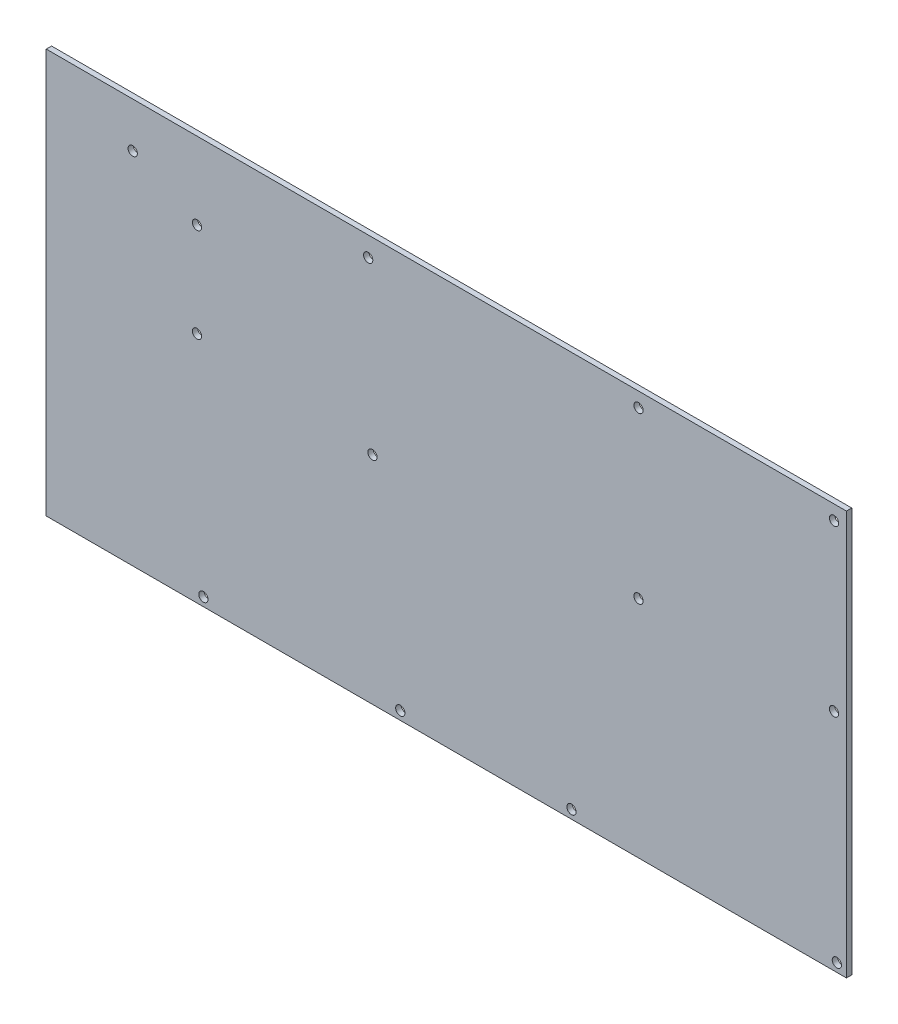
SolidWorks part; units mm, degrees
ref_plane "Front Plane" through (0, 0, 0) normal (0, 0, 1) x (1, 0, 0)
ref_plane "Top Plane" through (0, 0, 0) normal (0, 1, 0) x (1, 0, 0)
ref_plane "Right Plane" through (0, 0, 0) normal (1, 0, 0) x (0, 0, -1)
sketch "Sketch1" plane through (0, 0, 0) normal (0, 0, 1) x (1, 0, 0)
  line L0 (-51.1882, 19.6128) -> (-39.9222, 19.6128) construction
  line L1 (-39.9222, -40.382) -> (197.517, -40.382)
  line L2 (-39.9222, -40.382) -> (-39.9222, 79.6076)
  line L3 (-39.9222, 79.6076) -> (197.517, 79.6076)
  line L4 (197.517, -40.382) -> (197.517, 79.6076)
  line L5 (-51.1882, 26.9589) -> (-51.1882, 12.2667) construction
  line L6 (152.1018, -60.4872) -> (152.1018, -45.4872) construction
  circle A0 centre (193.834, 75.2896) radius 1.3716
  circle A1 centre (135.8154, 75.2896) radius 1.3716
  circle A2 centre (193.834, 26.293) radius 1.3716
  circle A3 centre (135.8204, 26.293) radius 1.3716
  circle A4 centre (194.6722, -37.842) radius 1.3716
  circle A5 centre (115.9322, -37.842) radius 1.3716
  circle A6 centre (55.6072, 73.791) radius 1.3716
  circle A7 centre (56.8772, 23.753) radius 1.3716
  circle A8 centre (65.1322, -37.842) radius 1.3716
  circle A9 centre (4.8072, 56.773) radius 1.3716
  circle A10 centre (4.8072, 28.833) radius 1.3716
  circle A11 centre (6.7122, -37.842) radius 1.3716
  circle A12 centre (-14.2718, 66.2672) radius 1.3716
  point P9 (-39.9222, 19.6128)
  dimension "D6" = 2.7432
  dimension "D8" = 2.7432
  dimension "D10" = 2.7432
  dimension "D13" = 2.7432
  dimension "D16" = 2.7432
  dimension "D19" = 2.7432
  dimension "D22" = 2.7432
  dimension "D25" = 2.7432
  dimension "D28" = 2.7432
  dimension "D31" = 2.7432
  dimension "D34" = 2.7432
  dimension "D37" = 2.7432
  dimension "D40" = 2.7432
  dimension "D1" = 119.9896
  dimension "D2" = 237.4392
  dimension "D3" = 45.4152
  dimension "D4" = 3.683
  dimension "D5" = 4.318
  dimension "D7" = 61.7017
  dimension "D9" = 4.318
  dimension "D11" = 3.683
  dimension "D12" = 53.3146
  dimension "D14" = 61.6966
  dimension "D15" = 53.3146
  dimension "D17" = 2.8448
  dimension "D18" = 117.4496
  dimension "D20" = 81.5848
  dimension "D21" = 117.4496
  dimension "D23" = 141.9098
  dimension "D24" = 5.8166
  dimension "D26" = 140.6398
  dimension "D27" = 55.8546
  dimension "D29" = 132.3848
  dimension "D30" = 117.4496
  dimension "D32" = 192.7098
  dimension "D33" = 22.8346
  dimension "D35" = 192.7098
  dimension "D36" = 50.7746
  dimension "D38" = 190.8048
  dimension "D39" = 117.4496
  dimension "D41" = 211.7888
extrude "Boss-Extrude1" add sketch "Sketch1" along normal blind 1.5748 from offset 6
